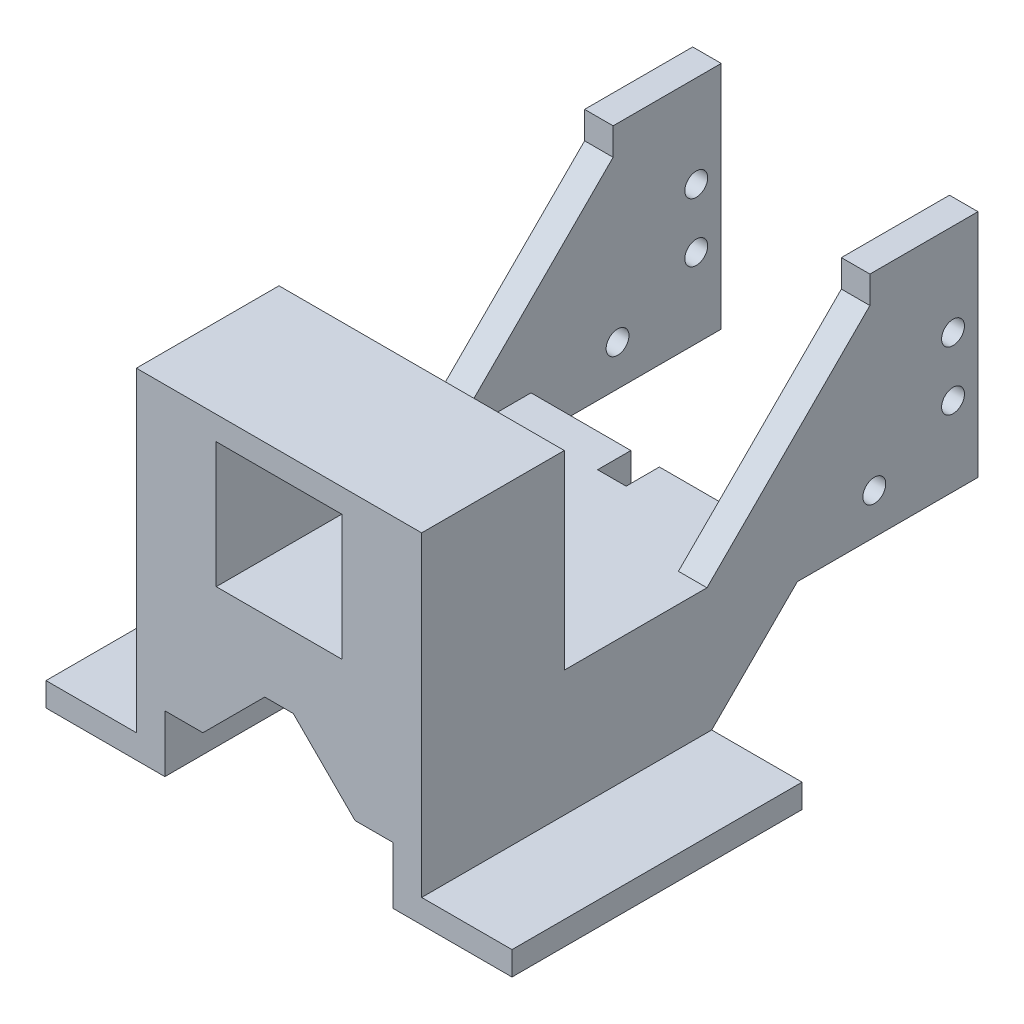
SolidWorks part; units mm, degrees
material "6061 Alloy"
ref_plane "Front Plane" through (0, 0, 0) normal (0, 0, 1) x (1, 0, 0)
ref_plane "Top Plane" through (0, 0, 0) normal (0, 1, 0) x (1, 0, 0)
ref_plane "Right Plane" through (0, 0, 0) normal (1, 0, 0) x (0, 0, -1)
sketch "Sketch1" plane through (0, 0, 0) normal (0, 0, 1) x (1, 0, 0)
  line L0 (-3, -41.4) -> (3, -41.4)
  line L5 (24, -54.4) -> (24, -66.4)
  line L6 (24, -66.4) -> (49, -66.4)
  line L7 (49, -66.4) -> (49, -61.4)
  line L8 (-13.2, 0) -> (13.2, 0)
  line L9 (13.2, 0) -> (13.2, -26.4)
  line L10 (49, -61.4) -> (30, -61.4)
  line L11 (30, -61.4) -> (30, 5)
  line L12 (0, 0) -> (0, 56.7042) construction
  line L18 (-30, -61.4) -> (-30, 5)
  line L19 (-49, -61.4) -> (-30, -61.4)
  line L20 (-13.2, 0) -> (-13.2, -26.4)
  line L21 (-49, -66.4) -> (-49, -61.4)
  line L22 (-24, -66.4) -> (-49, -66.4)
  line L23 (-24, -54.4) -> (-24, -66.4)
  line L25 (-30, 5) -> (30, 5)
  line L26 (-13.2, -26.4) -> (13.2, -26.4)
  line L27 (0, 0) -> (0, -112.3075) construction
  line L28 (-3, -41.4) -> (-16, -54.4)
  line L29 (3, -41.4) -> (16, -54.4)
  line L30 (-16, -54.4) -> (-24, -54.4)
  line L31 (16, -54.4) -> (24, -54.4)
  point P10 (0, 0)
  point P23 (0, 0)
  dimension "D1" = 13.2
  dimension "D2" = 15
  dimension "D3" = 40
  dimension "D4" = 60
  dimension "D5" = 6
  dimension "D6" = 5
  dimension "D7" = 5
  dimension "D8" = 12
  dimension "D11" = 25
  dimension "D12" = 26.4
  dimension "D13" = 3
  dimension "D14" = 3
  dimension "D15" = 45
  dimension "D16" = 45
extrude "Boss-Extrude1" add sketch "Sketch1" along normal blind 117
sketch "Sketch59" plane through (0, 0, 117) normal (0, 0, 1) x (1, 0, 0)
  line L0 (-13.2, 0) -> (13.2, -26.4) construction
  line L1 (13.2, 0) -> (-13.2, -26.4) construction
  circle A0 centre (-9.6645, -3.5355) radius 5
  circle A1 centre (-9.6645, -22.8645) radius 5
  circle A2 centre (9.6645, -3.5355) radius 5
  circle A3 centre (9.6645, -22.8645) radius 5
  dimension "D1" = 10
sketch "Sketch60" plane through (0, 0, 0) normal (0, 0, -1) x (-1, 0, 0)
  line L0 (-30, 5) -> (30, 5) construction
  line L1 (24, -35) -> (-24, -35)
  line L2 (24, -35) -> (24, 5)
  line L3 (24, 5) -> (-24, 5)
  line L4 (-24, -35) -> (-24, 5)
  line L5 (24, -35) -> (-24, 5) construction
  line L6 (24, 5) -> (-24, -35) construction
  point P0 (0, -15)
  point P5 (0, 0)
  point P7 (0, 0)
  point P8 (24, 5)
  point P11 (24, -73.7539)
  point P12 (24, -37.836)
  point P14 (0, 0)
  point P15 (0, 0)
  dimension "D1" = 48
  dimension "D2" = 40
extrude "Cut-Extrude1" cut sketch "Sketch60" against normal blind 87
sketch "Sketch61" plane through (-30, 0, 0) normal (-1, 0, 0) x (0, 0, 1)
  line L0 (0, -43.4) -> (38, -43.4)
  line L2 (38, -43.4) -> (56, -61.4)
  line L3 (117, -61.4) -> (0, -61.4) construction
  line L4 (56, -61.4) -> (0, -61.4)
  line L5 (0, -61.4) -> (0, -43.4)
  line L7 (0, 5) -> (0, -61.4) construction
  point P2 (6.5545, -43.4)
  point P4 (0, 0)
  point P10 (0, -43.4)
  dimension "D1" = 18
  dimension "D2" = 45
  dimension "D3" = 56
extrude "Cut-Extrude2" cut sketch "Sketch61" against normal through all
sketch "Sketch63" plane through (-30, 0, 0) normal (-1, 0, 0) x (0, 0, 1)
  line L0 (117, -13.2) -> (-18.3934, -13.2) construction
  line L1 (117, 5) -> (117, -61.4) construction
  line L2 (117, -26.4) -> (117, 0) construction
  point P6 (0, 0)
hole_wizard "M4 Clearance Hole1" positions "Sketch64" profile "Sketch65" hole size "M4" standard "ANSI Metric" end condition through all
sketch "Sketch64" plane through (-30, 0, 0) normal (-1, 0, 0) x (0, 0, 1)
  line L0 (117, -13.2) -> (-18.3934, -13.2) construction
  line L1 (0, 5) -> (0, -43.4) construction
  point P0 (5.25, -14.37)
  point P2 (5.25, -26.77)
  point P4 (21.8, -34.86)
  dimension "D1" = 12.4
  dimension "D2" = 1.17
  dimension "D3" = 16.55
  dimension "D4" = 8.09
  dimension "D5" = 5.25
sketch "Sketch65" plane through (-30, -14.37, 5.25) normal (0, 1, 0) x (0, 0, 1)
  line L0 (0, 0) -> (0, 79)
  line L1 (0, 79) -> (2.4, 79)
  line L2 (2.4, 79) -> (2.4, 0)
  line L5 (2.4, 0) -> (0, 0)
  line L11 (0, -6.35) -> (0, 107.95) construction
  dimension "Thru Hole Dia." = 4.8
  dimension "Thru Hole Depth" = 79
sketch "Sketch66" plane through (0, 0, 0) normal (0, 0, -1) x (-1, 0, 0)
  line L1 (24, -35) -> (-24, -35)
  line L2 (24, -35) -> (24, -66.2908)
  line L3 (24, -66.2908) -> (-24, -66.2908)
  line L4 (-24, -35) -> (-24, -66.2908)
  line L5 (-24, -35) -> (24, -35) construction
  point P5 (-24, -66.2908)
  point P7 (-24, -35)
  point P10 (-18.7172, -35)
  point P12 (0, 0)
  point P13 (0, 0)
extrude "Cut-Extrude3" cut sketch "Sketch66" against normal blind 40
sketch "Sketch68" plane through (-30, 0, 0) normal (-1, 0, 0) x (0, 0, 1)
  line L0 (22.7333, -0.7333) -> (57, -35)
  line L2 (117, 5) -> (0, 5) construction
  line L3 (87, 5) -> (22.7333, 5)
  line L4 (22.7333, 5) -> (22.7333, -0.7333)
  line L6 (57, -35) -> (57, 5) construction
  line L7 (87, 5) -> (87, -35)
  line L8 (87, -35) -> (57, -35)
  point P2 (91.3416, 5)
  point P7 (0, 0)
  point P10 (85.9043, 5)
  point P13 (51.314, -35)
  point P14 (28.0234, -15.9549)
  point P15 (19.3104, 2.8116)
  point P16 (0, 0)
  point P17 (0, 0)
  point P18 (30.0039, 5)
  point P19 (27.7333, 1.1583)
  point P21 (0, 0)
  dimension "D1" = 45
  dimension "D2" = 30
extrude "Cut-Extrude5" cut sketch "Sketch68" against normal through all
sketch "Sketch69" plane through (0, -61.4, 0) normal (0, 1, 0) x (1, 0, 0)
  line L0 (-49, -117) -> (-49, 0) construction
  line L1 (-49, -56) -> (49, -56)
  line L2 (-49, -56) -> (-49, 0)
  line L3 (-49, 0) -> (49, 0)
  line L4 (49, -56) -> (49, 0)
extrude "Cut-Extrude6" cut sketch "Sketch69" against normal through all
ref_plane "Plane1" through (-25.2104, -25.2104, 0) normal (-0.7071, -0.7071, 0) x (-0.7071, 0.7071, 0)
ref_plane "Plane2" through (25.2104, -25.2104, 0) normal (0.7071, -0.7071, 0) x (-0.7071, -0.7071, 0)
ref_axis "Axis1" through (0, -50.4208, 36.15) along (0, 0, 1)
sketch "Sketch70" plane through (0, -41.4, 0) normal (0, -1, 0) x (1, 0, 0)
  line L0 (3, 117) -> (3, 40) construction
  line L1 (-3, 40) -> (3, 40)
  line L2 (-3, 40) -> (-3, 47)
  line L3 (-3, 47) -> (3, 47)
  line L4 (3, 40) -> (3, 47)
  dimension "D1" = 7
extrude "Cut-Extrude7" cut sketch "Sketch70" against normal through all
ref_plane "Plane3" through (0, 11.7071, 11.7071) normal (0, 0.7071, 0.7071) x (1, 0, 0)
